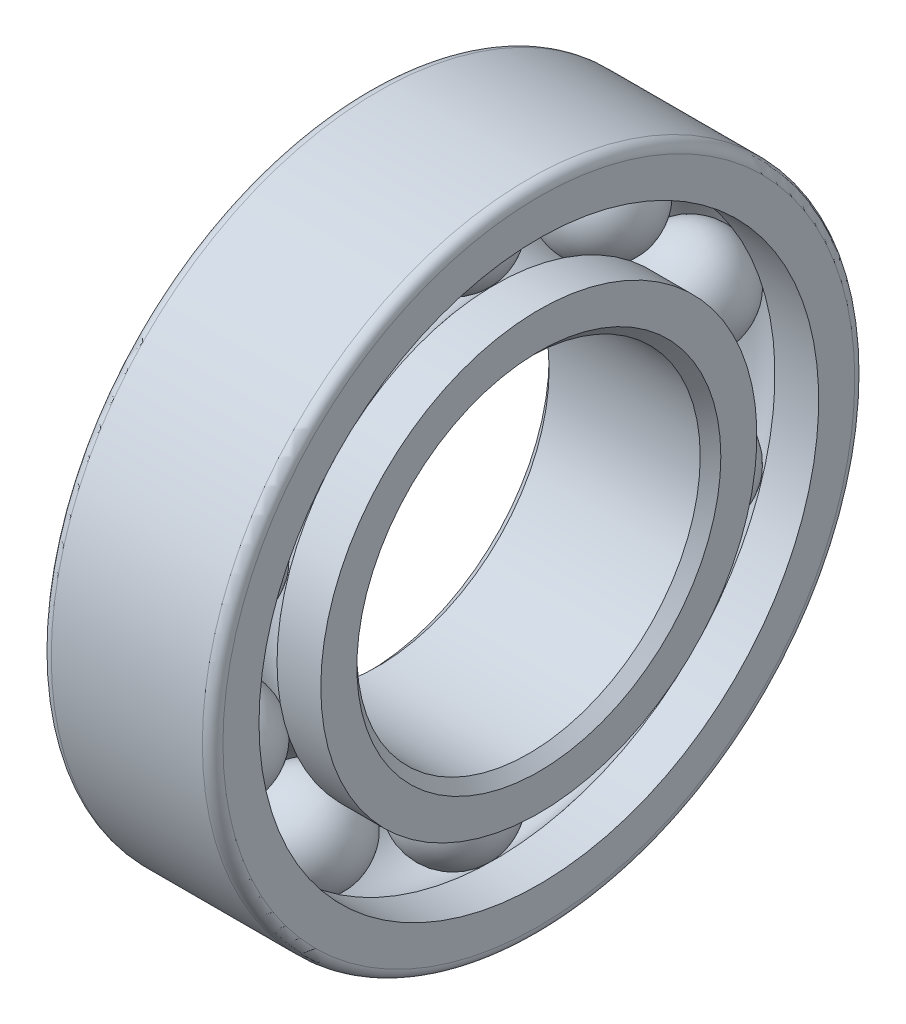
SolidWorks part; units mm, degrees
ref_plane "Front Plane" through (0, 0, 0) normal (0, 0, 1) x (1, 0, 0)
ref_plane "Top Plane" through (0, 0, 0) normal (0, 1, 0) x (1, 0, 0)
ref_plane "Right Plane" through (0, 0, 0) normal (1, 0, 0) x (0, 0, -1)
sketch "Sketch1" plane through (0, 0, 0) normal (0, 1, 0) x (1, 0, 0)
  line L0 (-10.3017, 0) -> (0, 0) construction
  line L1 (0, 0) -> (0, 8.825) construction
  line L3 (2.5, 9.5) -> (-2.5, 9.5)
  line L4 (2.5, 9.5) -> (2.5, 8.15)
  line L5 (2.5, 8.15) -> (-2.5, 8.15)
  line L6 (-2.5, 9.5) -> (-2.5, 8.15)
  line L7 (2.5, 9.5) -> (-2.5, 8.15) construction
  line L8 (2.5, 8.15) -> (-2.5, 9.5) construction
  line L9 (2.5, 6.35) -> (-2.5, 6.35)
  line L10 (2.5, 6.35) -> (2.5, 5)
  line L11 (2.5, 5) -> (-2.5, 5)
  line L12 (-2.5, 6.35) -> (-2.5, 5)
  line L13 (2.5, 6.35) -> (-2.5, 5) construction
  line L14 (2.5, 5) -> (-2.5, 6.35) construction
  circle A0 centre (0, 7.25) radius 1.5206
  point P9 (0, 5.675)
  dimension "D2" = 5
  dimension "D1" = 5
  dimension "D3" = 9.5
  dimension "D4" = 6.35
  dimension "D5" = 8.15
revolve "Revolve1" add sketch "Sketch1" angle 360 about L0 region at (0, 0, -8.904) region at (0, 0, -5.596)
ref_axis "Axis1" through (2.5, 0, 0) along (-1, 0, 0)
sketch "Sketch2" plane through (0, 0, 0) normal (0, 0, 1) x (1, 0, 0)
  line L0 (-1.5, 7.25) -> (1.5, 7.25)
  circle A0 centre (0, 7.25) radius 1.5
  dimension "D1" = 3
  dimension "D2" = 7.25
revolve "Revolve2" add sketch "Sketch2" angle 360 about L0 region at (0, 7.8866, 0)
pattern_circular "CirPattern2" count 10 over 360 about axis through (2.5, 0, 0) along (-1, 0, 0) of bodies 103
fillet "Fillet1" radius 0.3 2 edges at (2.5, 0, 9.5) (-2.5, 0, 9.5)
chamfer "Chamfer1" distance 0.3 angle 45 2 edges at (2.5, 0, 5) (-2.5, 0, 5)
